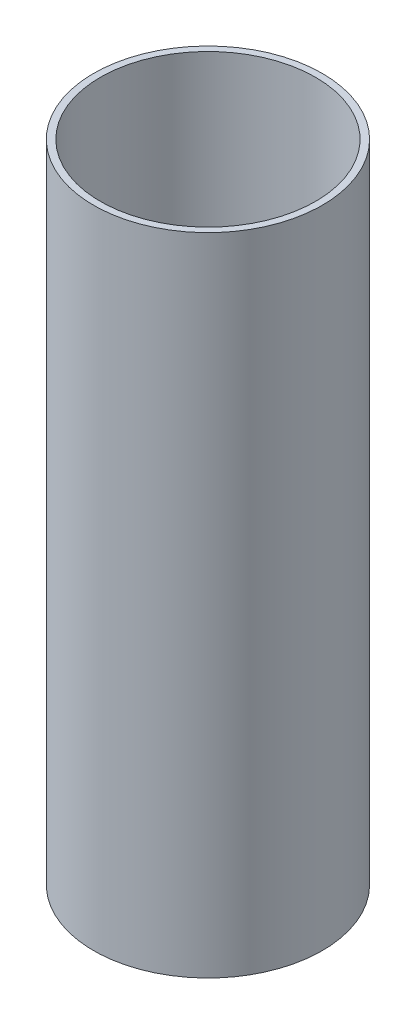
SolidWorks part; units mm, degrees
ref_plane "Front Plane" through (0, 0, 0) normal (0, 0, 1) x (1, 0, 0)
ref_plane "Top Plane" through (0, 0, 0) normal (0, 1, 0) x (1, 0, 0)
ref_plane "Right Plane" through (0, 0, 0) normal (1, 0, 0) x (0, 0, -1)
sketch "Sketch1" plane through (0, 0, 0) normal (0, 1, 0) x (1, 0, 0)
  circle A0 centre (0, 0) radius 101.6
  circle A1 centre (0, 0) radius 107.95
extrude "Boss-Extrude1" add sketch "Sketch1" along normal blind 609.6 contours A1 A0 region at (-104.8967, 0, 0)
